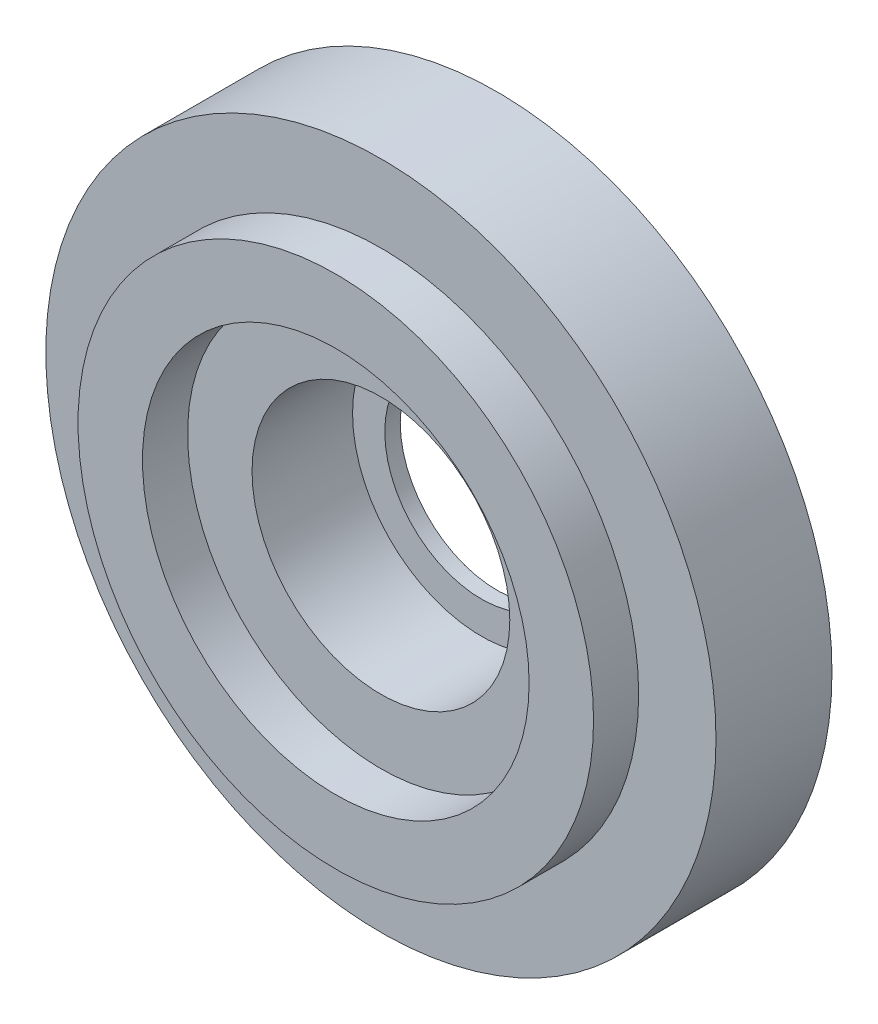
SolidWorks part; units mm, degrees
ref_plane "Front Plane" through (0, 0, 0) normal (0, 0, 1) x (1, 0, 0)
ref_plane "Top Plane" through (0, 0, 0) normal (0, 1, 0) x (1, 0, 0)
ref_plane "Right Plane" through (0, 0, 0) normal (1, 0, 0) x (0, 0, -1)
sketch "Sketch1" plane through (0, 0, 0) normal (0, 0, 1) x (1, 0, 0)
  circle A0 centre (0, 0) radius 6.35
  circle A1 centre (0, 0) radius 12.7
  dimension "D1" = 12.7
  dimension "D2" = 25.4
extrude "Boss-Extrude1" add sketch "Sketch1" along normal blind 10.16
ref_plane "Plane1" through (0, 0, 5.08) normal (0, 0, 1) x (1, 0, 0)
sketch "Sketch2" plane through (0, 0, 5.08) normal (0, 0, 1) x (1, 0, 0)
  circle A0 centre (0, 0) radius 6.35
  circle A1 centre (0, 0) radius 6.35 construction
  circle A2 centre (0, 0) radius 16.51
  dimension "D1" = 33.02
extrude "Boss-Extrude2" add sketch "Sketch2" along normal mid plane 5.715
sketch "Sketch3" plane through (0, 0, 10.16) normal (0, 0, 1) x (1, 0, 0)
  circle A0 centre (0, 0) radius 6.35
  circle A1 centre (0, 0) radius 9.525
  circle A2 centre (0, 0) radius 6.35 construction
  dimension "D1" = 19.05
extrude "Cut-Extrude1" cut sketch "Sketch3" against normal up to surface (2.2225 mm away) up to face at (16.51, 0, 7.9375)
sketch "Sketch4" plane through (0, 0, 0) normal (0, 0, -1) x (-1, 0, 0)
  circle A1 centre (0, 0) radius 9.525
  circle A2 centre (0, 0) radius 9.525
  dimension "D1" = 0
extrude "Cut-Extrude2" cut sketch "Sketch4" against normal up to surface (2.2225 mm away) up to face at (16.51, 0, 2.2225)
sketch "Sketch5" plane through (0, 0, 2.2225) normal (0, 0, -1) x (-1, 0, 0)
  circle A0 centre (0, 0) radius 6.35 construction
  circle A1 centre (0, 0) radius 6.35
  circle A2 centre (0, 0) radius 4.7625
  dimension "D1" = 9.525
extrude "Boss-Extrude3" add sketch "Sketch5" against normal blind 0.762 contours A1 | A2
